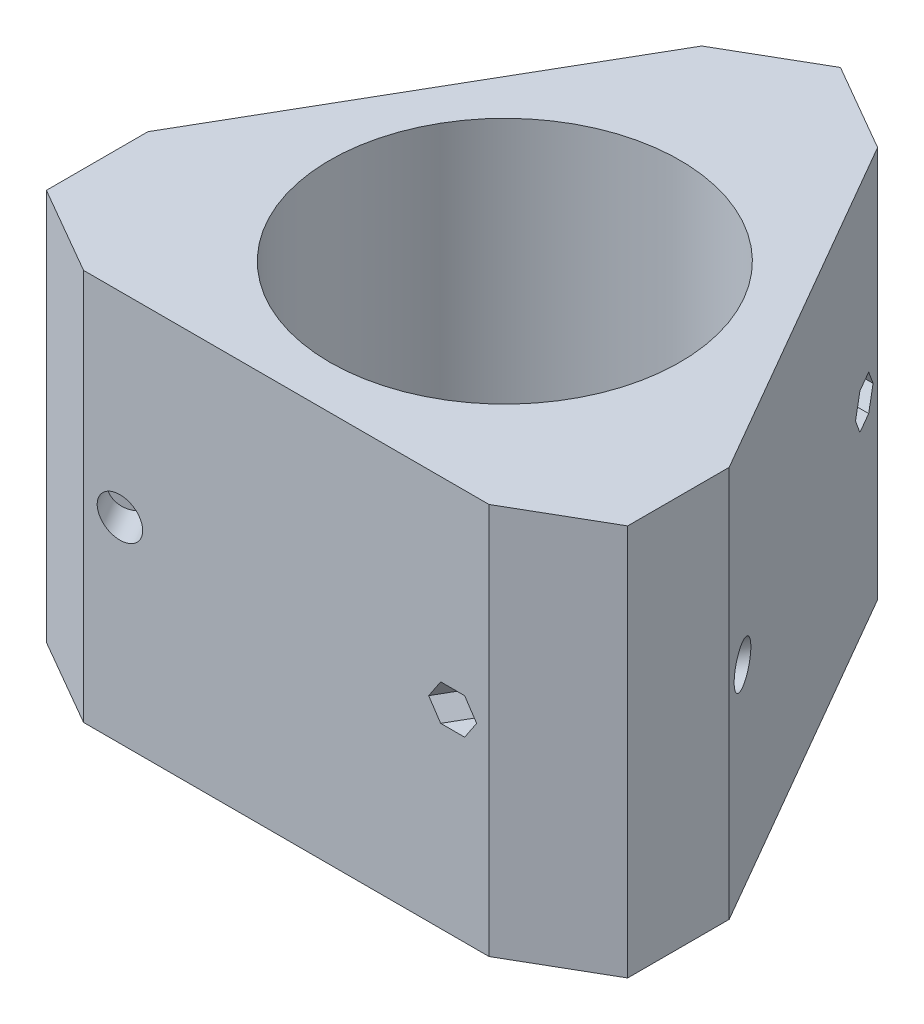
SolidWorks part; units mm, degrees
ref_plane "Front Plane" through (0, 0, 0) normal (0, 0, 1) x (1, 0, 0)
ref_plane "Top Plane" through (0, 0, 0) normal (0, 1, 0) x (1, 0, 0)
ref_plane "Right Plane" through (0, 0, 0) normal (1, 0, 0) x (0, 0, -1)
sketch "Sketch1" plane through (0, 0, 0) normal (0, 1, 0) x (1, 0, 0)
  line L20 (-84.8499, -19.3548) -> (-84.8499, -48.9881)
  line L21 (-84.8499, -48.9881) -> (-59.1867, -63.8048)
  line L22 (-59.1867, -63.8048) -> (59.1867, -63.8048)
  line L23 (59.1867, -63.8048) -> (84.8499, -48.9881)
  line L24 (84.8499, -48.9881) -> (84.8499, -19.3548)
  line L25 (84.8499, -19.3548) -> (25.6632, 83.1596)
  line L26 (25.6632, 83.1596) -> (0, 97.9763)
  line L27 (0, 97.9763) -> (-25.6632, 83.1596)
  line L28 (-25.6632, 83.1596) -> (-84.8499, -19.3548)
  line L29 (84.8499, -48.9881) -> (-55.2566, 31.9024)
  line L30 (55.2566, 31.9024) -> (-84.8499, -48.9881)
  line L31 (0, -63.8048) -> (0, 97.9763)
  circle A0 centre (0, 0) radius 51.1048
  point P13 (0, 0)
  point P20 (-44.2581, 25.5524)
  dimension "D1" = 102.2096
  dimension "D2" = 44.45
  dimension "D3" = 12.7
sketch "Sketch2" plane through (0, 0, 0) normal (0, 1, 0) x (1, 0, 0)
  line L0 (84.8499, -48.9881) -> (-55.2566, 31.9024) construction
  line L1 (59.1867, -63.8048) -> (84.8499, -48.9881) construction
  line L2 (-59.1867, -63.8048) -> (59.1867, -63.8048) construction
  line L3 (55.2566, 31.9024) -> (-84.8499, -48.9881) construction
  line L4 (-84.8499, -48.9881) -> (-59.1867, -63.8048) construction
  line L5 (84.8499, -48.9881) -> (-55.2566, 31.9024)
  line L6 (59.1867, -63.8048) -> (84.8499, -48.9881)
  line L7 (-59.1867, -63.8048) -> (59.1867, -63.8048)
  line L8 (55.2566, 31.9024) -> (-84.8499, -48.9881)
  line L9 (-84.8499, -48.9881) -> (-59.1867, -63.8048)
  line L10 (-64.0554, -36.9824) -> (-47.7703, -65.1891)
  line L13 (-54.0554, -54.3029) -> (-49.0757, -51.4279)
  line L14 (-49.0757, -51.4279) -> (-41.9299, -63.8048)
  line L15 (-41.9299, -63.8048) -> (-46.9096, -66.6798)
  line L16 (-46.9096, -66.6798) -> (-47.7703, -65.1891)
  line L17 (0, -55) -> (0, 55) construction
  line L21 (-64.0554, -36.9824) -> (-67.0865, -38.7324)
  line L22 (67.0865, -38.7324) -> (64.0554, -36.9824)
  line L23 (-46.9096, -66.6798) -> (-47.7703, -65.1891)
  line L24 (-61.0243, -35.2324) -> (-43.8785, -64.9298)
  line L25 (-61.0243, -35.2324) -> (-64.0554, -36.9824)
  circle A0 centre (0, 0) radius 51.1048 construction
  circle A1 centre (0, 0) radius 51.1048
  point P11 (-44.2581, -25.5524)
  dimension "D1" = 22.86
  dimension "D3" = 5.75
  dimension "D4" = 20
  dimension "D2" = 3.5
extrude "Boss-Extrude1" add sketch "Sketch1" along normal mid plane 114.3 contours A0 L30 L21 L22 L31 | A0 L31 L22 L23 L29 region at (-42.3912, 0, 50.0899) region at (42.3912, 0, 50.0899)
revolve "Cut-Revolve7" cut sketch "Sketch2" angle 360 about L10 region at (-46.2293, 0, 64.8686) region at (-49.4946, 0, 58.6041) region at (-57.5399, 0, 44.7677)
revolve "Cut-Revolve8" cut sketch "Sketch2<7>" angle 360 about L10 region at (-46.6215, 0, 57.8931)
sketch "Sketch2<7>" plane through (0, 0, 0) normal (0, 1, 0) x (1, 0, 0) same geometry as "Sketch2"
mirror "Mirror1" about plane through (0, 0, 0) normal (1, 0, 0) of "Cut-Revolve7"
sketch "Sketch3" plane through (0, 0, 0) normal (0.5, 0, -0.866) x (-0.866, 0, -0.5)
  line L1 (-76.9959, 5.25) -> (-80.027, 0)
  line L2 (-80.027, 0) -> (-76.9959, -5.25)
  line L3 (-76.9959, -5.25) -> (-70.9337, -5.25)
  line L4 (-70.9337, -5.25) -> (-67.9026, 0)
  line L5 (-67.9026, 0) -> (-70.9337, 5.25)
  line L6 (-70.9337, 5.25) -> (-76.9959, 5.25)
  circle A0 centre (-73.9648, 0) radius 3.5 construction
  circle A1 centre (-73.9648, 0) radius 3.5
  circle A2 centre (-73.9648, 0) radius 5.25 construction
  dimension "D1" = 10.5
extrude "Cut-Extrude1" cut sketch "Sketch3" against normal through all from offset 16 offset against normal yes
ref_axis "Axis1" through (0, 57.15, 0) along (0, -1, 0)
pattern_circular "CirPattern1" count 3 over 360 about axis through (0, 57.15, 0) along (0, -1, 0) of "Cut-Extrude1", "Cut-Revolve8", "Cut-Revolve7", "Boss-Extrude1", "Mirror1"
equation "\"Tube_Diameter_With_Tolerance\"= 4.024"
equation "\"Vertical_Surface_Height\"= 1.75in"
equation "\"D1@Sketch1\"=\"Tube_Diameter_With_Tolerance\""
equation "\"D2@Sketch1\"=\"Vertical_Surface_Height\""
equation "\"Offset_From_Diameter\"= .5in"
equation "\"D3@Sketch1\"=\"Offset_From_Diameter\""
equation "\"Thread_Center\"= 1.8 * \"Offset_From_Diameter\""
equation "\"M6_Thread_Clearance\"= 7mm"
equation "\"M6_Head_Clearance\"= 11.5mm"
equation "\"M6_Nut_Flat_To_Flat\"= 10.5mm"
equation "\"Nut_Start\"= 16mm"
equation "\"D1@Sketch2\"=\"Thread_Center\""
equation "\"D3@Sketch2\"=\"M6_Head_Clearance\"/2"
equation "\"D4@Sketch2\"=\"Screw_Head_Start\""
equation "\"Length\"= 4.5in"
equation "\"D1@Boss-Extrude1\"=\"Length\""
equation "\"D2@Sketch2\"=\"M6_Thread_Clearance\"/2"
equation "\"D1@Sketch3\"=\"M6_Nut_Flat_To_Flat\""
equation "\"D19@Cut-Extrude1\"=\"Nut_Start\""
equation "\"Screw_Head_Start\"= 20mm"
